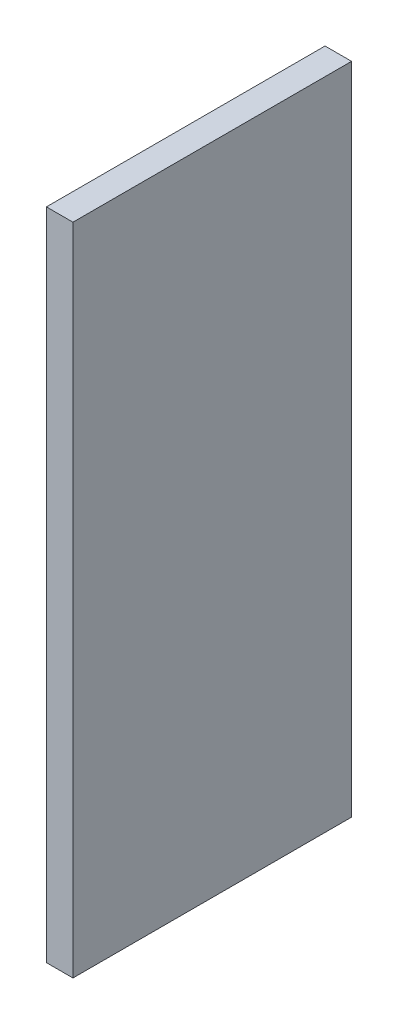
SolidWorks part; units mm, degrees
ref_plane "Спереди" through (0, 0, 0) normal (0, 0, 1) x (1, 0, 0)
ref_plane "Сверху" through (0, 0, 0) normal (0, 1, 0) x (1, 0, 0)
ref_plane "Справа" through (0, 0, 0) normal (1, 0, 0) x (0, 0, -1)
other "Configuration Table"
sketch "Эскиз1" plane through (0, 0, 0) normal (0, 0, 1) x (1, 0, 0)
  line L1 (0, 0) -> (3, 0)
  line L2 (0, 0) -> (0, 74)
  line L3 (0, 74) -> (3, 74)
  line L4 (3, 0) -> (3, 74)
extrude "Бобышка-Вытянуть1" add sketch "Эскиз1" along normal blind 31.5
